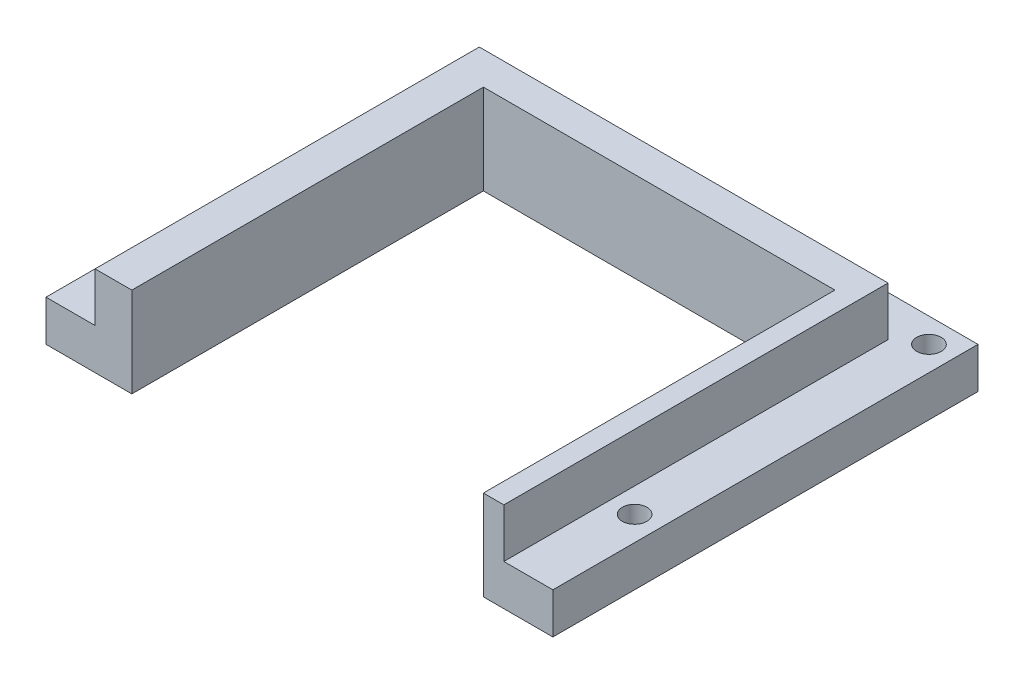
SolidWorks part; units mm, degrees
ref_plane "Ön Düzlem" through (0, 0, 0) normal (0, 0, 1) x (1, 0, 0)
ref_plane "Üst Düzlem" through (0, 0, 0) normal (0, 1, 0) x (1, 0, 0)
ref_plane "Sağ Düzlem" through (0, 0, 0) normal (1, 0, 0) x (0, 0, -1)
sketch "Çizim1" plane through (0, 0, 0) normal (0, 1, 0) x (1, 0, 0)
  line L1 (0, 0) -> (62, 0)
  line L2 (0, 0) -> (0, 52)
  line L3 (0, 52) -> (62, 52)
  line L4 (62, 0) -> (62, 52)
  line L5 (6, 0) -> (56, 0)
  line L6 (6, 0) -> (6, 47)
  line L7 (6, 47) -> (56, 47)
  line L8 (56, 0) -> (56, 47)
  circle A0 centre (16.5, 5.5) radius 2
  circle A1 centre (47.5, 5.5) radius 2
  circle A2 centre (16.5, 36.5) radius 2
  circle A3 centre (47.5, 36.5) radius 2
  circle A4 centre (3, 49) radius 1.5
  circle A5 centre (59, 49) radius 1.5
  circle A6 centre (59, 13) radius 1.5
  circle A7 centre (3, 13) radius 1.5
  dimension "D7" = 4
  dimension "D6" = 3
  dimension "D1" = 52
  dimension "D2" = 62
  dimension "D3" = 6
  dimension "D4" = 5
  dimension "D5" = 6
  dimension "D8" = 31
  dimension "D9" = 31
  dimension "D10" = 5.5
  dimension "D11" = 8.5
  dimension "D12" = 3
  dimension "D13" = 3
  dimension "D14" = 3
  dimension "D15" = 3
  dimension "D16" = 13
  dimension "D17" = 13
  dimension "D18" = 3
  dimension "D19" = 3
extrude "Yükseklik-Ekstrüzyon1" add sketch "Çizim1" along normal blind 5 contours L8 L1 L4 L3 L2 L6 L7 A7 A6 A5 A4 region at (0.8092, 0, -26)
extrude "Yükseklik-Ekstrüzyon2" add sketch "Çizim1<3>" along normal blind 11 contours L1 L8 L7 L6 A3 A2 A1 A0 region at (30.9781, 0, -23.5546)
sketch "Çizim1<3>" plane through (0, 0, 0) normal (0, 1, 0) x (1, 0, 0) same geometry as "Çizim1"
sketch "Çizim4" plane through (0, 0, 0) normal (0, 1, 0) x (1, 0, 0)
  line L0 (6, 0) -> (56, 0) construction
  line L1 (53.5, 0) -> (10.5, 0)
  line L2 (53.5, 0) -> (53.5, 43)
  line L3 (53.5, 43) -> (10.5, 43)
  line L4 (10.5, 0) -> (10.5, 43)
  line L5 (56, 0) -> (56, 47) construction
  circle A0 centre (16.5, 36.5) radius 2
  circle A1 centre (47.5, 36.5) radius 2
  circle A2 centre (47.5, 5.5) radius 2
  circle A3 centre (16.5, 5.5) radius 2
  circle A4 centre (16.5, 5.5) radius 2 construction
  point P22 (0, 0)
  dimension "D1" = 43
  dimension "D2" = 43
  dimension "D3" = 2.5
extrude "Kes-Ekstrüzyon9" cut sketch "Çizim4" along normal blind 20
